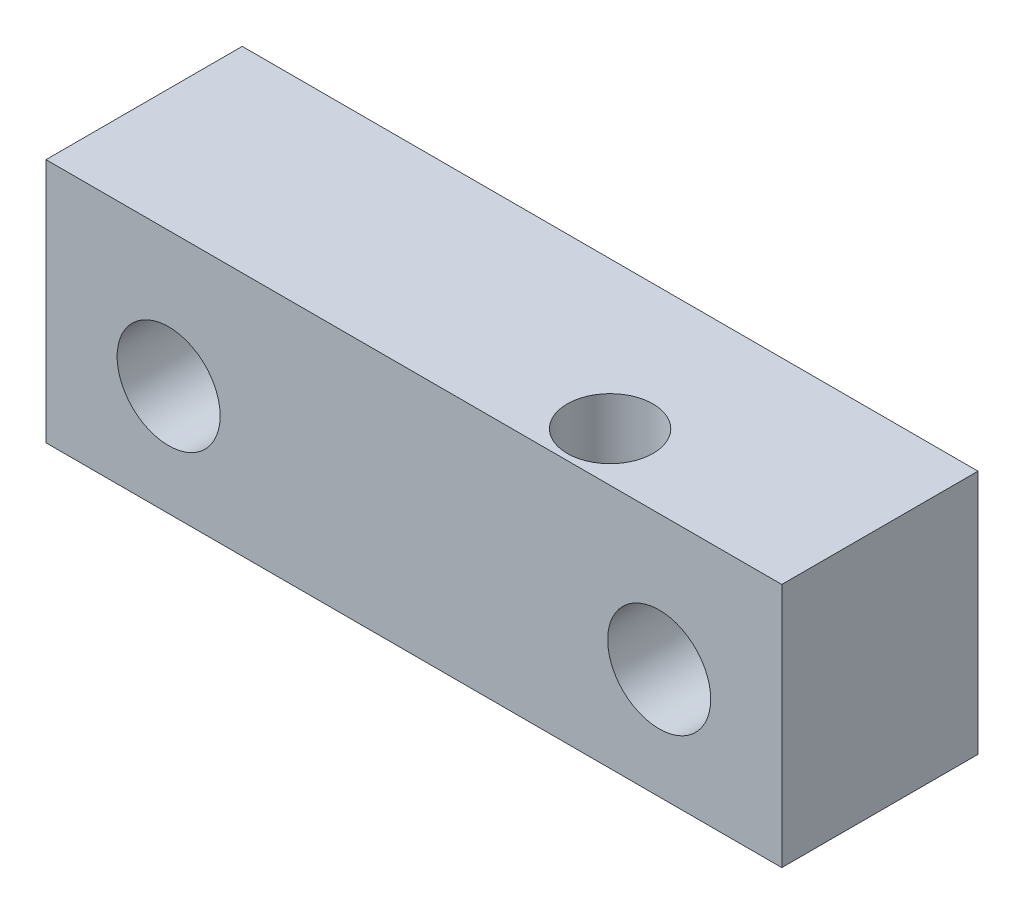
SolidWorks part; units mm, degrees
ref_plane "Front Plane" through (0, 0, 0) normal (0, 0, 1) x (1, 0, 0)
ref_plane "Top Plane" through (0, 0, 0) normal (0, 1, 0) x (1, 0, 0)
ref_plane "Right Plane" through (0, 0, 0) normal (1, 0, 0) x (0, 0, -1)
sketch "Sketch1" plane through (0, 0, 0) normal (0, 1, 0) x (1, 0, 0)
  line L0 (6, -2) -> (6, -4) construction
  line L5 (-15, 4) -> (15, 4)
  line L6 (-15, 4) -> (-15, -4)
  line L7 (-15, -4) -> (15, -4)
  line L8 (15, 4) -> (15, -4)
  line L9 (-15, 4) -> (15, -4) construction
  line L10 (-15, -4) -> (15, 4) construction
  line L11 (0, 0) -> (6, 0) construction
  circle A0 centre (6, -2) radius 1.75
  point P0 (0, 0)
  dimension "D3" = 3.5
  dimension "D1" = 30
  dimension "D2" = 8
  dimension "D4" = 2
  dimension "D5" = 6
extrude "Boss-Extrude1" add sketch "Sketch1" along normal blind 2
sketch "Sketch2" plane through (0, 0, 4) normal (0, 0, 1) x (1, 0, 0)
  line L0 (-10, -3.5) -> (10, -3.5) construction
  line L2 (-15, 0) -> (-15, -8)
  line L5 (15, 0) -> (5, 0)
  line L6 (15, 0) -> (15, -8)
  line L7 (15, -8) -> (-15, -8)
  line L9 (-15, 0) -> (5, 0)
  line L10 (-15, 2) -> (15, 2) construction
  line L11 (-15, 0) -> (15, 0) construction
  circle A0 centre (-10, -3.5) radius 2.1
  circle A1 centre (10, -3.5) radius 2.1
  point P13 (10, 0)
  point P17 (0, -3.5)
  point P22 (0, 0)
  dimension "D1" = 4.2
  dimension "D2" = 4.2
  dimension "D3" = 5.5
  dimension "D4" = 8
  dimension "D5" = 20
extrude "Boss-Extrude2" add sketch "Sketch2" against normal up to surface (8 mm away) up to face at (0, 1, -4)
sketch "Sketch4" plane through (0, 0, 0) normal (0, 1, 0) x (1, 0, 0)
  circle A1 centre (6, -2) radius 1.75
  circle A2 centre (6, -2) radius 1.75
  dimension "D1" = 0
extrude "Cut-Extrude2" cut sketch "Sketch4" against normal offset from surface (2 mm away) 4 up to face at (0, 2, 0)
sketch "Sketch5" plane through (0, 0, -4) normal (0, 0, -1) x (-1, 0, 0)
  line L0 (15, 2) -> (15, -8) construction
  line L1 (-15, -8) -> (15, -8)
  line L2 (-15, -8) -> (-15, 0)
  line L3 (-15, 0) -> (15, 0)
  line L4 (15, -8) -> (15, 0)
extrude "Boss-Extrude3" add sketch "Sketch5" against normal offset from surface (4 mm away) 4 up to face at (0, -3, 4)
